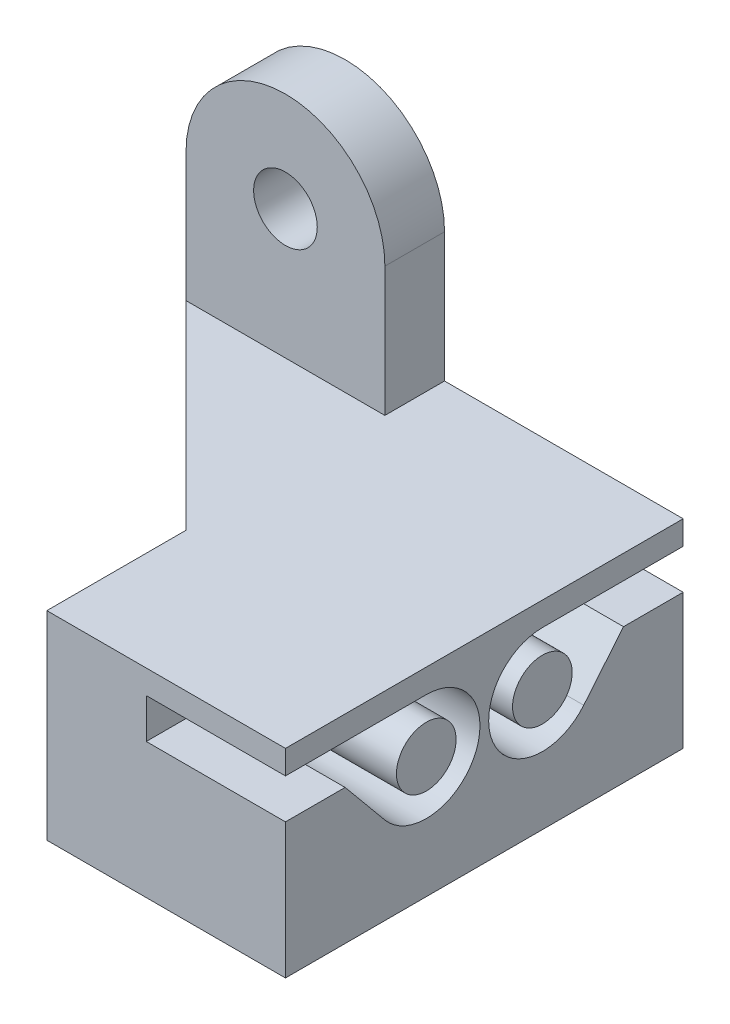
SolidWorks part; units mm, degrees
material "ABS"
ref_plane "Plano frontal" through (0, 0, 0) normal (0, 0, 1) x (1, 0, 0)
ref_plane "Plano superior" through (0, 0, 0) normal (0, 1, 0) x (1, 0, 0)
ref_plane "Plano direito" through (0, 0, 0) normal (1, 0, 0) x (0, 0, -1)
sketch "Esboço1" plane through (0, 0, 0) normal (0, 0, 1) x (1, 0, 0)
  line L0 (0, 12.5) -> (0, -12.5) construction
  line L1 (5, 12.5) -> (5, 6)
  line L2 (-5, 12.5) -> (-5, -12.5)
  line L3 (5, -4) -> (17, -4)
  line L4 (17, -4) -> (17, 6)
  line L5 (17, 6) -> (5, 6)
  line L6 (5, -4) -> (5, -12.5)
  arc A0 (5, 12.5) -> (-5, 12.5) centre (0, 12.5) ccw
  arc A1 (-5, -12.5) -> (5, -12.5) centre (0, -12.5) ccw
  circle A2 centre (0, -12.5) radius 1.6
  circle A3 centre (0, 12.5) radius 1.6
  point P0 (0, 0)
  point P2 (0, 0)
  dimension "D2" = 3.2
  dimension "D3" = 5
  dimension "D1" = 25
  dimension "D4" = 4
  dimension "D5" = 12
  dimension "D6" = 10
extrude "Ressalto-extrusão1" add sketch "Esboço1" along normal blind 20
sketch "Esboço2" plane through (0, 0, 20) normal (0, 0, 1) x (1, 0, 0)
  line L1 (-5, -18.1063) -> (5, -18.1063)
  line L2 (-5, -18.1063) -> (-5, 18.1063)
  line L3 (-5, 18.1063) -> (5, 18.1063)
  line L4 (5, -18.1063) -> (5, 18.1063)
  line L5 (-5, -18.1063) -> (5, 18.1063) construction
  line L6 (-5, 18.1063) -> (5, -18.1063) construction
  point P0 (0, 0)
extrude "Corte-extrusão1" cut sketch "Esboço2" against normal offset from surface (17 mm away) 3 up to face at (5.5, 0.5, 0)
chamfer "Chanfro1" distance 10 angle 45 1 edges at (5, 1, 3)
sketch "Esboço3" plane through (17, 0, 0) normal (1, 0, 0) x (0, 0, -1)
  line L0 (-10, 6) -> (-10, -4) construction
  line L1 (-20, 6) -> (0, 6) construction
  line L2 (-20, -4) -> (0, -4) construction
  line L3 (0, 4.8) -> (-7.0812, 4.8)
  line L4 (0, -4) -> (0, 6) construction
  line L5 (-5, 0.38) -> (-3, 2.8)
  line L6 (-3, 2.8) -> (0, 2.8)
  line L7 (0, 4.8) -> (0, 2.8)
  line L8 (-20, 4.8) -> (-20, 2.8)
  line L9 (-17, 2.8) -> (-20, 2.8)
  line L10 (-15, 0.38) -> (-17, 2.8)
  line L11 (-20, 4.8) -> (-12.9188, 4.8)
  arc A0 (-7.0812, 4.8) -> (-5, 0.38) centre (-7.0812, 2.1) ccw
  circle A1 centre (-7.0812, 2.1) radius 1.5
  circle A2 centre (-12.9188, 2.1) radius 1.5
  arc A3 (-12.9188, 4.8) -> (-15, 0.38) centre (-12.9188, 2.1) cw
  point P15 (-10, -4)
  dimension "D3" = 1.2
  dimension "D4" = 3
  dimension "D1" = 1.2
  dimension "D2" = 2
  dimension "D5" = 3
  dimension "D6" = 2
extrude "Corte-extrusão2" cut sketch "Esboço3" against normal blind 7
